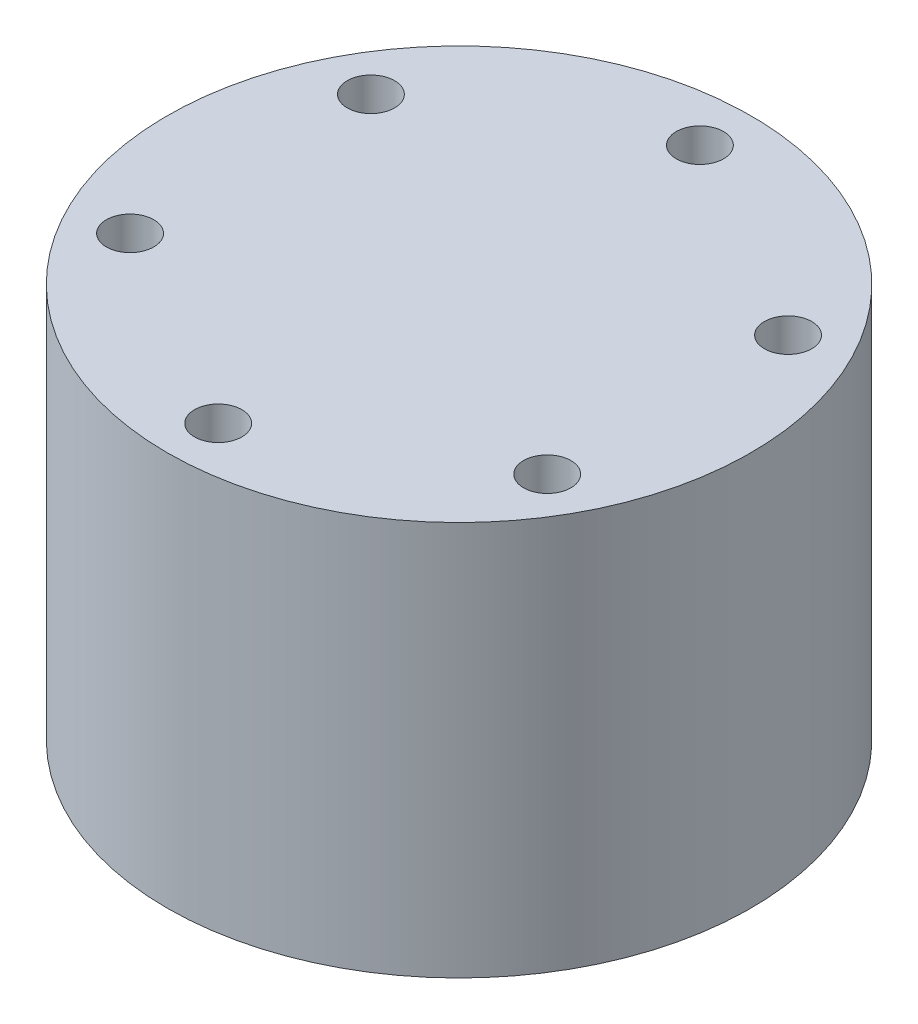
SolidWorks part; units mm, degrees
ref_plane "Front Plane" through (0, 0, 0) normal (0, 0, 1) x (1, 0, 0)
ref_plane "Top Plane" through (0, 0, 0) normal (0, 1, 0) x (1, 0, 0)
ref_plane "Right Plane" through (0, 0, 0) normal (1, 0, 0) x (0, 0, -1)
sketch "Sketch1" plane through (0, 0, 0) normal (0, 1, 0) x (1, 0, 0)
  circle A0 centre (0, 0) radius 18.5
  dimension "D1" = 37
extrude "Boss-Extrude1" add sketch "Sketch1" along normal blind 25
sketch "Sketch2" plane through (0, 25, 0) normal (0, 1, 0) x (1, 0, 0)
  circle A0 centre (0, 0) radius 15.265
  circle A1 centre (0, 15.265) radius 1.5
  circle A2 centre (13.2199, 7.6325) radius 1.5
  circle A3 centre (13.2199, -7.6325) radius 1.5
  circle A4 centre (0, -15.265) radius 1.5
  circle A5 centre (-13.2199, -7.6325) radius 1.5
  circle A6 centre (-13.2199, 7.6325) radius 1.5
  point P18 (0, 0)
  dimension "D1" = 30.53
  dimension "D2" = 3
  dimension "D3" = 6
extrude "Cut-Extrude1" cut sketch "Sketch2" against normal blind 10 contours A0 A1 | A0 A6 | A0 A6 | A0 A1 | A0 A2 | A0 A2 | A0 A3 | A0 A3 | A0 A4 | A0 A4 | A0 A5 | A0 A5 region at (12.6572, 25, -7.3076) region at (13.7596, 25, -7.9441) region at (13.7596, 25, 7.9441) region at (12.6572, 25, 7.3076) region at (0, 25, -14.6153) region at (0, 25, -15.8882) region at (0, 25, 15.8882) region at (0, 25, 14.6153) region at (-12.6572, 25, -7.3076) region at (-13.7596, 25, -7.9441) region at (-13.7596, 25, 7.9441) region at (-12.6572, 25, 7.3076)
